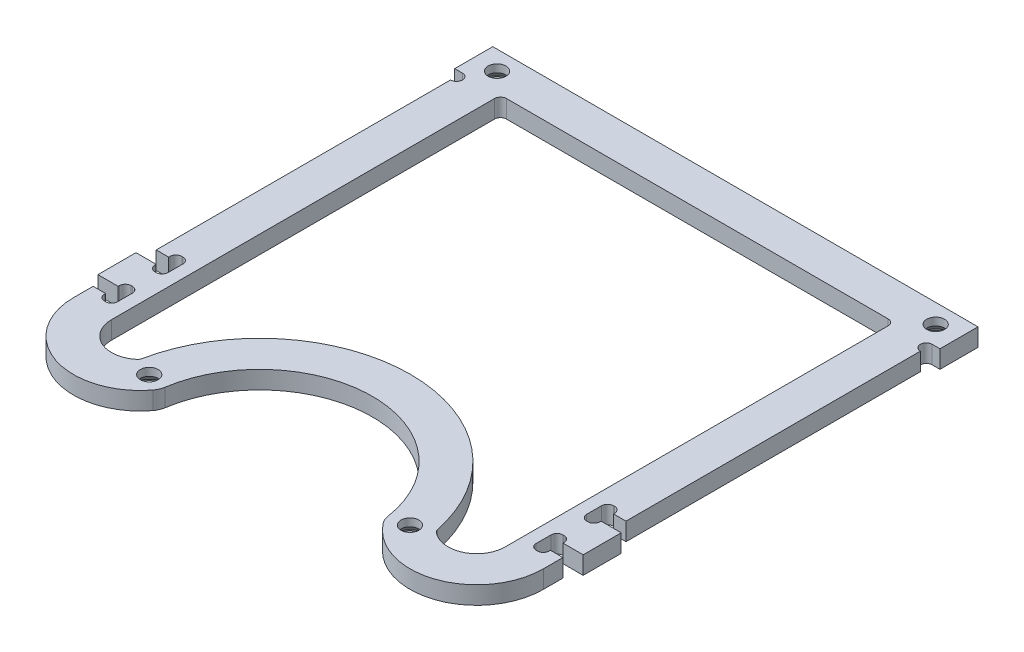
SolidWorks part; units mm, degrees
ref_plane "Front Plane" through (0, 0, 0) normal (0, 0, 1) x (1, 0, 0)
ref_plane "Top Plane" through (0, 0, 0) normal (0, 1, 0) x (1, 0, 0)
ref_plane "Right Plane" through (0, 0, 0) normal (1, 0, 0) x (0, 0, -1)
sketch "Sketch1" plane through (0, 0, 0) normal (0, 1, 0) x (1, 0, 0)
  line L0 (-36.88, 36.725) -> (36.88, 36.725) construction
  line L1 (36.88, 36.725) -> (21.92, -36.725) construction
  line L2 (21.92, -36.725) -> (-21.92, -36.725) construction
  line L3 (-21.92, -36.725) -> (-36.88, 36.725) construction
  line L4 (0, -40.095) -> (0, -36.725) construction
  line L5 (0, 36.725) -> (0, -36.725) construction
  line L6 (-39.5, -14.675) -> (-39.5, 33.525)
  line L7 (-33.1, -14.675) -> (-33.1, 33.525)
  line L8 (-39.5, 9.425) -> (-33.1, 9.425) construction
  line L9 (0, 33.525) -> (0, 39.925) construction
  line L10 (-39.5, -23.275) -> (-33.1, -23.275) construction
  line L13 (40.8, 33.525) -> (-40.8, 33.525)
  line L14 (40.8, 33.525) -> (40.8, 39.925)
  line L15 (40.8, 39.925) -> (-40.8, 39.925)
  line L16 (-40.8, 33.525) -> (-40.8, 39.925)
  line L17 (40.8, 33.525) -> (-40.8, 39.925) construction
  line L18 (40.8, 39.925) -> (-40.8, 33.525) construction
  line L19 (39.5, 33.525) -> (-39.5, 33.525)
  line L20 (39.5, 33.525) -> (39.5, 39.925)
  line L21 (39.5, 39.925) -> (-39.5, 39.925)
  line L22 (-39.5, 33.525) -> (-39.5, 39.925)
  line L23 (39.5, 33.525) -> (-39.5, 39.925) construction
  line L24 (39.5, 39.925) -> (-39.5, 33.525) construction
  line L27 (-35.2, -25.275) -> (-37.4, -25.275)
  line L28 (-39.5, -20.075) -> (-40.8, -20.075)
  line L29 (-35.2, -16.775) -> (-35.2, -14.675) construction
  line L30 (-33.1, -31.875) -> (-39.5, -31.875)
  line L31 (-33.1, -31.875) -> (-33.1, -14.675)
  line L32 (-33.1, -14.675) -> (-39.5, -14.675)
  line L33 (-39.5, -31.875) -> (-39.5, -14.675)
  line L34 (-33.1, -31.875) -> (-39.5, -14.675) construction
  line L35 (-33.1, -14.675) -> (-39.5, -31.875) construction
  line L36 (-39.5, -20.075) -> (-37.4, -20.075)
  line L37 (-39.5, -20.075) -> (-39.5, -17.975)
  line L38 (-39.5, -17.975) -> (-37.4, -17.975)
  line L39 (-37.4, -20.075) -> (-37.4, -17.975)
  line L40 (-37.4, -19.025) -> (-39.5, -19.025) construction
  line L41 (-37.4, -19.025) -> (-33.1, -19.025) construction
  line L42 (-36.3, -31.875) -> (-36.3, -14.675) construction
  line L43 (-35.2, -21.275) -> (-37.4, -21.275)
  line L44 (-35.2, -21.275) -> (-35.2, -16.775)
  line L45 (-35.2, -16.775) -> (-37.4, -16.775)
  line L46 (-37.4, -21.275) -> (-37.4, -16.775)
  line L47 (-35.2, -21.275) -> (-37.4, -16.775) construction
  line L48 (-35.2, -16.775) -> (-37.4, -21.275) construction
  line L53 (-35.2, -25.275) -> (-35.2, -29.775)
  line L58 (-35.2, -29.775) -> (-37.4, -29.775)
  line L67 (39.5, -17.975) -> (37.4, -17.975)
  line L68 (-37.4, -25.275) -> (-37.4, -29.775)
  line L69 (-39.5, -28.575) -> (-37.4, -28.575)
  line L70 (-39.5, -20.075) -> (-39.5, -26.475)
  line L71 (-39.5, -26.475) -> (-40.8, -26.475)
  line L72 (-40.8, -20.075) -> (-40.8, -26.475)
  line L73 (-39.5, -20.075) -> (-40.8, -26.475) construction
  line L74 (-39.5, -26.475) -> (-40.8, -20.075) construction
  line L75 (-39.5, -26.475) -> (-37.4, -26.475)
  line L76 (39.5, -20.075) -> (37.4, -20.075)
  line L77 (39.5, -28.575) -> (37.4, -28.575)
  line L78 (39.5, -26.475) -> (37.4, -26.475)
  line L79 (37.4, -25.275) -> (37.4, -29.775)
  line L80 (35.2, -29.775) -> (37.4, -29.775)
  line L81 (35.2, -25.275) -> (35.2, -29.775)
  line L82 (35.2, -25.275) -> (37.4, -25.275)
  line L83 (35.2, -21.275) -> (37.4, -21.275)
  line L84 (35.2, -21.275) -> (35.2, -16.775)
  line L85 (35.2, -16.775) -> (37.4, -16.775)
  line L86 (37.4, -21.275) -> (37.4, -16.775)
  line L87 (39.5, -17.975) -> (37.4, -17.975)
  line L88 (39.5, -20.075) -> (40.8, -20.075)
  line L89 (40.8, -20.075) -> (40.8, -26.475)
  line L90 (39.5, -26.475) -> (40.8, -26.475)
  line L91 (39.5, -31.875) -> (39.5, -14.675)
  line L92 (33.1, -31.875) -> (33.1, -14.675)
  line L93 (33.1, -14.675) -> (33.1, 33.525)
  line L94 (39.5, -14.675) -> (39.5, 33.525)
  circle A0 centre (21.92, -36.725) radius 1.5
  circle A1 centre (-21.92, -36.725) radius 1.5
  circle A2 centre (-36.88, 36.725) radius 1.5
  circle A3 centre (36.88, 36.725) radius 1.5
  circle A4 centre (-36.88, 36.725) radius 3.2
  circle A5 centre (-21.92, -36.725) radius 3.2
  circle A6 centre (21.92, -36.725) radius 3.2
  circle A7 centre (36.88, 36.725) radius 3.2
  circle A8 centre (0, -40.095) radius 16
  circle A9 centre (0, -40.095) radius 25.3775
  circle A10 centre (0, -40.095) radius 18.9775
  arc A11 (-39.5, -31.875) -> (-19.3737, -38.6631) centre (-28.2921, -31.875) ccw
  arc A12 (-33.1, -31.875) -> (-24.4663, -34.7869) centre (-28.2921, -31.875) ccw
  arc A13 (33.1, -31.875) -> (24.4663, -34.7869) centre (28.2921, -31.875) cw
  arc A14 (39.5, -31.875) -> (19.3737, -38.6631) centre (28.2921, -31.875) cw
  circle A15 centre (-39.5, 32.525) radius 1
  circle A16 centre (39.5, 32.525) radius 1
  point P10 (0, 0)
  point P26 (0, -23.275)
  point P29 (-40.15, -23.275)
  point P37 (-36.3, -23.275)
  point P53 (-36.3, -19.025)
  point P101 (0, 0)
  dimension "D4" = 3
  dimension "D5" = 6.4
  dimension "D6" = 32
  dimension "D11" = 2
  dimension "D1" = 74.958
  dimension "D2" = 43.84
  dimension "D3" = 73.76
  dimension "D7" = 3.37
  dimension "D8" = 81.6
  dimension "D9" = 60
  dimension "D10" = 79
  dimension "D12" = 2.1
  dimension "D13" = 2.2
  dimension "D14" = 4.5
extrude "Shape" add sketch "Sketch1" along normal blind 3 contours A13 A9 A12 A5 A10 A6 | A5 A1 | A9 A11 A5 | A12 A9 A5 | A12 L30 A11 A9 | L33 L75 L68 L27 L53 L58 L69 L30 L31 L32 L38 L46 L45 L44 L43 L36 | L28 L72 L71 L33 | A15 L6 L32 L7 L13 L19 | A4 L22 L15 L16 L13 | A4 L21 L22 | A4 L22 A2 | L22 A4 | A4 L22 L19 | A7 L21 A4 L13 L19 | A7 L20 A3 | A7 L20 L13 L14 L15 | L20 A7 | A7 L13 L20 | L94 A16 L13 L19 L93 L92 A13 A9 A14 L91 L77 L79 L80 L81 L82 L78 L76 L86 L83 L84 L85 L67 | A7 L20 L15 | L91 L90 L89 L88 | A9 A13 A6 | A6 A0 | A14 A9 A6 region at (-36.2858, 0, -9.3068) region at (-36.0672, 0, 23.275) region at (-38.8761, 0, -33.9129) region at (-40.2377, 0, -36.725) region at (0, 0, -36.725) region at (-32.2904, 0, 37.7071) region at (-40.15, 0, 23.275) region at (-38.3167, 0, -33.9628) region at (-39.7339, 0, -36.725) region at (35.4284, 0, 5.7836) region at (-24.8633, 0, 35.4035) region at (0, 0, 15.2643) region at (-38.8761, 0, -39.5371) region at (38.8761, 0, -33.9129) region at (33.7665, 0, -36.725) region at (-23.7462, 0, 40.4359) region at (24.8633, 0, 35.4035) region at (-24.7821, 0, 35.5096) region at (40.2377, 0, -36.725) region at (38.8761, 0, -39.5371) region at (39.7339, 0, -36.725) region at (23.7462, 0, 40.4359) region at (25.0204, 0, 36.4881) region at (40.15, 0, 23.275)
fillet "Mill fillets" radius 1 20 edges at (37.4, 1.5, 21.275) (35.2, 1.5, 21.275) (35.2, 1.5, 16.775) (37.4, 1.5, 16.775) (37.4, 1.5, 25.275) (35.2, 1.5, 25.275) (37.4, 1.5, 29.775) (35.2, 1.5, 29.775) (-37.4, 1.5, 21.275) (-35.2, 1.5, 21.275) (-35.2, 1.5, 16.775) (-37.4, 1.5, 16.775) (-37.4, 1.5, 25.275) (-35.2, 1.5, 25.275) (-35.2, 1.5, 29.775) (-37.4, 1.5, 29.775) (-24.921, 1.5, 35.303) (24.921, 1.5, 35.303) (33.1, 1.5, -33.525) (-33.1, 1.5, -33.525)
hole_wizard "M3 countersunks" positions "Sketch2" profile "Sketch3" countersink size "M3" standard "ANSI Metric" end condition through all
sketch "Sketch2" plane through (0, 0, 0) normal (0, -1, 0) x (-1, 0, 0)
  point P0 (21.92, -36.725)
  point P3 (-21.92, -36.725)
  point P6 (-36.88, 36.725)
  point P9 (36.88, 36.725)
sketch "Sketch3" plane through (-21.92, 0, 36.725) normal (1, 0, 0) x (0, 0, -1)
  line L0 (0, 0) -> (0, 3)
  line L1 (0, 3) -> (1.5, 3)
  line L2 (1.5, 3) -> (1.5, 1.7)
  line L3 (1.5, 1.7) -> (3, 0.2)
  line L4 (3, 0.2) -> (3, 0)
  line L6 (3, 0) -> (0, 0)
  line L7 (-1.5, 1.7) -> (-3, 0.2) construction
  line L11 (0, -6.35) -> (0, 107.95) construction
  dimension "Thru Hole Dia." = 3
  dimension "Thru Hole Depth" = 3
  dimension "C'Sink Dia." = 6
  dimension "C'Sink Angle" = 90
  dimension "Head Clearance" = 0.2
